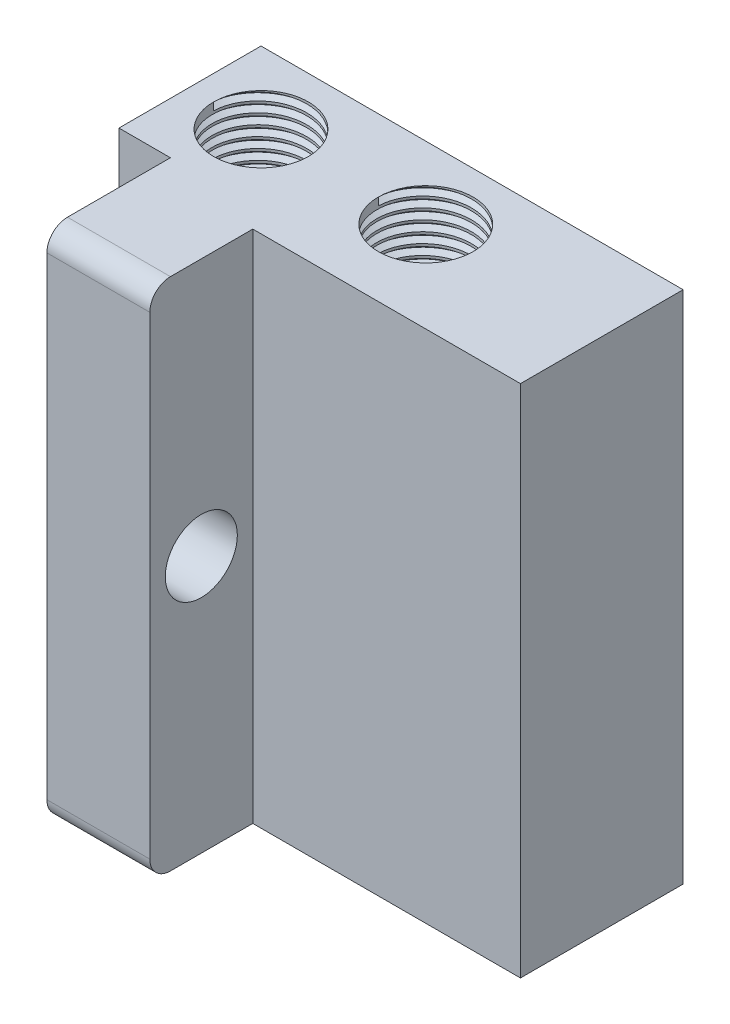
SolidWorks part; units mm, degrees
ref_plane "Front Plane" through (0, 0, 0) normal (0, 0, 1) x (1, 0, 0)
ref_plane "Top Plane" through (0, 0, 0) normal (0, 1, 0) x (1, 0, 0)
ref_plane "Right Plane" through (0, 0, 0) normal (1, 0, 0) x (0, 0, -1)
sketch "Sketch1" plane through (0, 0, 0) normal (0, 0, 1) x (1, 0, 0)
  line L1 (0, 0) -> (52.07, 0)
  line L2 (0, 0) -> (0, 63.5)
  line L3 (0, 63.5) -> (52.07, 63.5)
  line L4 (52.07, 0) -> (52.07, 63.5)
  dimension "D1" = 63.5
  dimension "D2" = 52.07
extrude "Boss-Extrude1" add sketch "Sketch1" along normal blind 20.066
sketch "Sketch2" plane through (0, 63.5, 0) normal (0, 1, 0) x (1, 0, 0)
  line L0 (0, -8.89) -> (52.07, -8.89) construction
  line L3 (0, -20.066) -> (0, 0) construction
  line L4 (52.07, -20.066) -> (52.07, 0) construction
  line L5 (52.07, 0) -> (0, 0) construction
  circle A0 centre (8.89, -8.89) radius 5.842
  circle A1 centre (29.21, -8.89) radius 5.842
  dimension "D1" = 11.684
  dimension "D2" = 11.684
  dimension "D3" = 8.89
  dimension "D4" = 8.89
  dimension "D5" = 29.21
extrude "Cut-Extrude1" cut sketch "Sketch2" against normal blind 50.8
thread "Thread1" pitch 1.27 method cut profile "Thread Profile1" start angle 0, offset 0, length 17.78, pitch 1.27, diameter 11.684
ref_plane "Plane4" through (3.048, 63.5, 8.89) normal (0, 0, 1) x (-1, 0, 0)
sketch "Thread Profile1" plane through (3.048, 63.5, 8.89) normal (0, 0, 1) x (-1, 0, 0)
  line L0 (0, 0) -> (0, 1.27) construction
  line L1 (0, 0) -> (0.6874, 0.3969)
  line L2 (0.6874, 0.3969) -> (0.6874, 0.5556)
  line L3 (0.6874, 0.5556) -> (0, 0.9525)
  line L4 (0.6874, 0.4762) -> (0, 0.4762) construction
  line L11 (0, 0) -> (0, 0.9525)
  point P2 (0, 0)
  dimension "Pitch" = 1.27
  dimension "Profile_Angle" = 60
  dimension "Profile_Land" = 0.1588
  dimension "Profile_Height" = 0.6874
thread "Thread2" pitch 1.27 method cut profile "Thread Profile2" start angle 0, offset 0, length 17.78, pitch 1.27, diameter 11.684
ref_plane "Plane5" through (23.368, 63.5, 8.89) normal (0, 0, 1) x (-1, 0, 0)
sketch "Thread Profile2" plane through (23.368, 63.5, 8.89) normal (0, 0, 1) x (-1, 0, 0)
  line L0 (0, 0) -> (0, 1.27) construction
  line L1 (0, 0) -> (0.6874, 0.3969)
  line L2 (0.6874, 0.3969) -> (0.6874, 0.5556)
  line L3 (0.6874, 0.5556) -> (0, 0.9525)
  line L4 (0.6874, 0.4762) -> (0, 0.4762) construction
  line L11 (0, 0) -> (0, 0.9525)
  point P2 (0, 0)
  dimension "Pitch" = 1.27
  dimension "Profile_Angle" = 60
  dimension "Profile_Land" = 0.1588
  dimension "Profile_Height" = 0.6874
sketch "Sketch3" plane through (0, 0, 20.066) normal (0, 0, 1) x (1, 0, 0)
  line L0 (6.35, 63.5) -> (6.35, 0)
  line L1 (52.07, 63.5) -> (0, 63.5) construction
  line L2 (0, 0) -> (52.07, 0) construction
  line L3 (6.35, 0) -> (0, 0)
  line L4 (0, 0) -> (0, 63.5)
  line L5 (0, 63.5) -> (6.35, 63.5)
  dimension "D1" = 6.35
extrude "Cut-Extrude2" cut sketch "Sketch3" against normal blind 2.54
sketch "Sketch4" plane through (0, 0, 20.066) normal (0, 0, 1) x (1, 0, 0)
  line L0 (6.35, 31.75) -> (52.07, 31.75) construction
  line L1 (6.35, 0) -> (6.35, 63.5) construction
  line L2 (52.07, 0) -> (52.07, 63.5) construction
  line L3 (6.35, 0) -> (52.07, 0) construction
  line L4 (6.35, 0) -> (19.05, 0)
  line L5 (6.35, 0) -> (6.35, 63.5)
  line L6 (6.35, 63.5) -> (19.05, 63.5)
  line L7 (19.05, 0) -> (19.05, 63.5)
  line L8 (12.7, 63.5) -> (12.7, 0) construction
  line L9 (6.35, 31.75) -> (19.05, 31.75) construction
  point P6 (12.7, 31.75)
  dimension "D1" = 12.7
extrude "Boss-Extrude2" add sketch "Sketch4" along normal blind 12.7
sketch "Sketch5" plane through (19.05, 0, 0) normal (1, 0, 0) x (0, 0, -1)
  line L0 (-26.416, 63.5) -> (-26.416, 0) construction
  line L1 (-32.766, 63.5) -> (-20.066, 63.5) construction
  line L2 (-32.766, 0) -> (-20.066, 0) construction
  circle A0 centre (-26.416, 31.75) radius 4.445
  dimension "D1" = 8.89
extrude "Cut-Extrude3" cut sketch "Sketch5" against normal blind 10.16
fillet "Fillet1" radius 2.54 2 edges at (12.7, 0, 32.766) (12.7, 63.5, 32.766)
